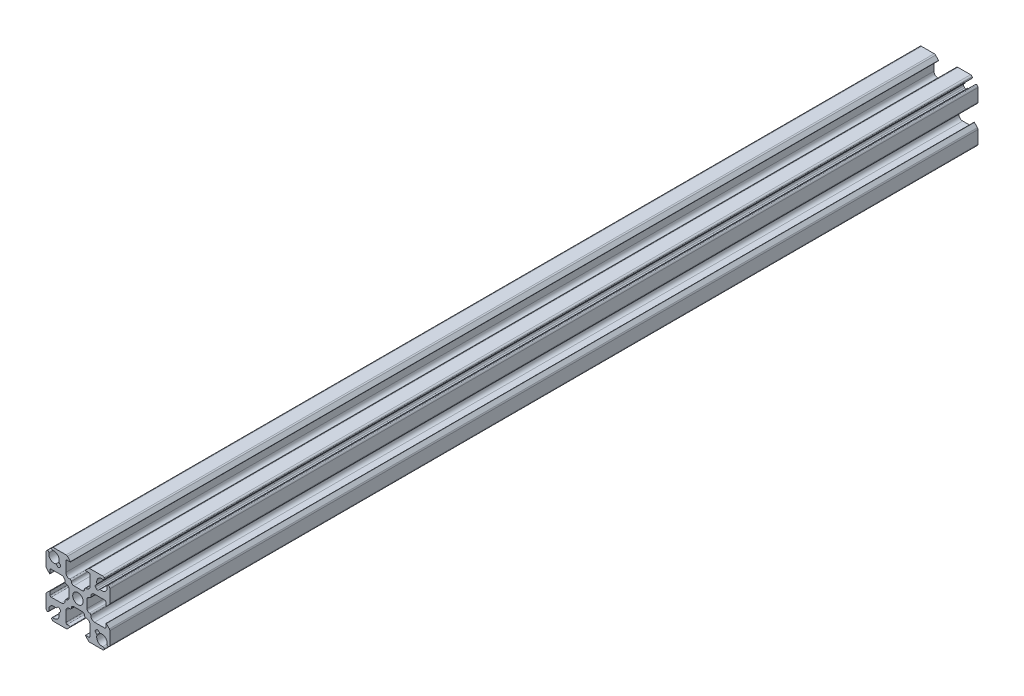
SolidWorks part; units mm, degrees
ref_plane "Front Plane" through (0, 0, 0) normal (0, 0, 1) x (1, 0, 0)
ref_plane "Top Plane" through (0, 0, 0) normal (0, 1, 0) x (1, 0, 0)
ref_plane "Right Plane" through (0, 0, 0) normal (1, 0, 0) x (0, 0, -1)
ref_plane "Plane1" through (0, 0, 0) normal (0, 0, -1) x (-1, 0, 0)
sketch "Sketch1" plane through (0, 0, 0) normal (0, 0, -1) x (-1, 0, 0)
  line L0 (-7.4885, 8.6199) -> (-6.9856, 8.117)
  line L1 (-6.9856, 7.4099) -> (-7.4099, 6.9856)
  line L2 (-8.117, 6.9856) -> (-8.6199, 7.4885)
  line L3 (-12.7, 9.7594) -> (-12.7, 4.7107)
  line L4 (-12.4803, 4.1803) -> (-11.2707, 2.9707)
  line L5 (-11.1, 3.0414) -> (-11.1, 4.325)
  line L6 (-10.6, 4.825) -> (-6.6, 4.825)
  line L7 (-5.1, 3.325) -> (-5.1, 3.15)
  line L8 (-3.6, 1.65) -> (-3.6, -1.65)
  line L9 (-5.1, -3.15) -> (-5.1, -3.325)
  line L10 (-6.6, -4.825) -> (-10.6, -4.825)
  line L11 (-11.1, -4.325) -> (-11.1, -3.0414)
  line L12 (-11.2707, -2.9707) -> (-12.4803, -4.1803)
  line L13 (-12.7, -4.7107) -> (-12.7, -9.7594)
  line L14 (-8.6199, -7.4885) -> (-8.117, -6.9856)
  line L15 (-7.4099, -6.9856) -> (-6.9856, -7.4099)
  line L16 (-6.9856, -8.117) -> (-7.4885, -8.6199)
  line L17 (-9.7594, -12.7) -> (-4.7107, -12.7)
  line L18 (-4.1803, -12.4803) -> (-2.9707, -11.2707)
  line L19 (-3.0414, -11.1) -> (-4.325, -11.1)
  line L20 (-4.825, -10.6) -> (-4.825, -6.6)
  line L21 (-3.325, -5.1) -> (-3.15, -5.1)
  line L22 (-1.65, -3.6) -> (1.65, -3.6)
  line L23 (3.15, -5.1) -> (3.325, -5.1)
  line L24 (4.825, -6.6) -> (4.825, -10.6)
  line L25 (4.325, -11.1) -> (3.0414, -11.1)
  line L26 (2.9707, -11.2707) -> (4.1803, -12.4803)
  line L27 (4.7107, -12.7) -> (9.7594, -12.7)
  line L28 (7.4885, -8.6199) -> (6.9856, -8.117)
  line L29 (6.9856, -7.4099) -> (7.4099, -6.9856)
  line L30 (8.117, -6.9856) -> (8.6199, -7.4885)
  line L31 (12.7, -9.7594) -> (12.7, -4.7107)
  line L32 (12.4803, -4.1803) -> (11.2707, -2.9707)
  line L33 (11.1, -3.0414) -> (11.1, -4.325)
  line L34 (10.6, -4.825) -> (6.6, -4.825)
  line L35 (5.1, -3.325) -> (5.1, -3.15)
  line L36 (3.6, -1.65) -> (3.6, 1.65)
  line L37 (5.1, 3.15) -> (5.1, 3.325)
  line L38 (6.6, 4.825) -> (10.6, 4.825)
  line L39 (11.1, 4.325) -> (11.1, 3.0414)
  line L40 (11.2707, 2.9707) -> (12.4803, 4.1803)
  line L41 (12.7, 4.7107) -> (12.7, 9.7594)
  line L42 (8.6199, 7.4885) -> (8.117, 6.9856)
  line L43 (7.4099, 6.9856) -> (6.9856, 7.4099)
  line L44 (6.9856, 8.117) -> (7.4885, 8.6199)
  line L45 (9.7594, 12.7) -> (4.7107, 12.7)
  line L46 (4.1803, 12.4803) -> (2.9707, 11.2707)
  line L47 (3.0414, 11.1) -> (4.325, 11.1)
  line L48 (4.825, 10.6) -> (4.825, 6.6)
  line L49 (3.325, 5.1) -> (3.15, 5.1)
  line L50 (1.65, 3.6) -> (-1.65, 3.6)
  line L51 (-3.15, 5.1) -> (-3.325, 5.1)
  line L52 (-4.825, 6.6) -> (-4.825, 10.6)
  line L53 (-4.325, 11.1) -> (-3.0414, 11.1)
  line L54 (-2.9707, 11.2707) -> (-4.1803, 12.4803)
  line L55 (-4.7107, 12.7) -> (-9.7594, 12.7)
  circle A0 centre (0, 0) radius 2.08
  arc A1 (-9.7594, 12.7) -> (-10.4266, 12.2927) centre (-9.7594, 11.95) ccw
  arc A2 (-10.4266, 12.2927) -> (-9.8933, 11.5721) centre (-9.9818, 12.0642) ccw
  arc A3 (-9.8933, 11.5721) -> (-7.5492, 8.8748) centre (-9.525, 9.525) cw
  arc A4 (-7.5492, 8.8748) -> (-7.4885, 8.6199) centre (-7.3118, 8.7967) ccw
  arc A5 (-6.9856, 8.117) -> (-6.9856, 7.4099) centre (-7.3392, 7.7635) cw
  arc A6 (-7.4099, 6.9856) -> (-8.117, 6.9856) centre (-7.7635, 7.3392) cw
  arc A7 (-8.6199, 7.4885) -> (-8.8748, 7.5492) centre (-8.7967, 7.3118) ccw
  arc A8 (-8.8748, 7.5492) -> (-11.5721, 9.8933) centre (-9.525, 9.525) cw
  arc A9 (-11.5721, 9.8933) -> (-12.2927, 10.4266) centre (-12.0642, 9.9818) ccw
  arc A10 (-12.2927, 10.4266) -> (-12.7, 9.7594) centre (-11.95, 9.7594) ccw
  arc A11 (-12.7, 4.7107) -> (-12.4803, 4.1803) centre (-11.95, 4.7107) ccw
  arc A12 (-11.2707, 2.9707) -> (-11.1, 3.0414) centre (-11.2, 3.0414) ccw
  arc A13 (-11.1, 4.325) -> (-10.6, 4.825) centre (-10.6, 4.325) cw
  arc A14 (-6.6, 4.825) -> (-5.1, 3.325) centre (-6.6, 3.325) cw
  arc A15 (-5.1, 3.15) -> (-4.6, 2.65) centre (-4.6, 3.15) ccw
  arc A16 (-4.6, 2.65) -> (-3.6, 1.65) centre (-4.6, 1.65) cw
  arc A17 (-3.6, -1.65) -> (-4.6, -2.65) centre (-4.6, -1.65) cw
  arc A18 (-4.6, -2.65) -> (-5.1, -3.15) centre (-4.6, -3.15) ccw
  arc A19 (-5.1, -3.325) -> (-6.6, -4.825) centre (-6.6, -3.325) cw
  arc A20 (-10.6, -4.825) -> (-11.1, -4.325) centre (-10.6, -4.325) cw
  arc A21 (-11.1, -3.0414) -> (-11.2707, -2.9707) centre (-11.2, -3.0414) ccw
  arc A22 (-12.4803, -4.1803) -> (-12.7, -4.7107) centre (-11.95, -4.7107) ccw
  arc A23 (-12.7, -9.7594) -> (-12.2927, -10.4266) centre (-11.95, -9.7594) ccw
  arc A24 (-12.2927, -10.4266) -> (-11.5721, -9.8933) centre (-12.0642, -9.9818) ccw
  arc A25 (-11.5721, -9.8933) -> (-8.8748, -7.5492) centre (-9.525, -9.525) cw
  arc A26 (-8.8748, -7.5492) -> (-8.6199, -7.4885) centre (-8.7967, -7.3118) ccw
  arc A27 (-8.117, -6.9856) -> (-7.4099, -6.9856) centre (-7.7635, -7.3392) cw
  arc A28 (-6.9856, -7.4099) -> (-6.9856, -8.117) centre (-7.3392, -7.7635) cw
  arc A29 (-7.4885, -8.6199) -> (-7.5492, -8.8748) centre (-7.3118, -8.7967) ccw
  arc A30 (-7.5492, -8.8748) -> (-9.8933, -11.5721) centre (-9.525, -9.525) cw
  arc A31 (-9.8933, -11.5721) -> (-10.4266, -12.2927) centre (-9.9818, -12.0642) ccw
  arc A32 (-10.4266, -12.2927) -> (-9.7594, -12.7) centre (-9.7594, -11.95) ccw
  arc A33 (-4.7107, -12.7) -> (-4.1803, -12.4803) centre (-4.7107, -11.95) ccw
  arc A34 (-2.9707, -11.2707) -> (-3.0414, -11.1) centre (-3.0414, -11.2) ccw
  arc A35 (-4.325, -11.1) -> (-4.825, -10.6) centre (-4.325, -10.6) cw
  arc A36 (-4.825, -6.6) -> (-3.325, -5.1) centre (-3.325, -6.6) cw
  arc A37 (-3.15, -5.1) -> (-2.65, -4.6) centre (-3.15, -4.6) ccw
  arc A38 (-2.65, -4.6) -> (-1.65, -3.6) centre (-1.65, -4.6) cw
  arc A39 (1.65, -3.6) -> (2.65, -4.6) centre (1.65, -4.6) cw
  arc A40 (2.65, -4.6) -> (3.15, -5.1) centre (3.15, -4.6) ccw
  arc A41 (3.325, -5.1) -> (4.825, -6.6) centre (3.325, -6.6) cw
  arc A42 (4.825, -10.6) -> (4.325, -11.1) centre (4.325, -10.6) cw
  arc A43 (3.0414, -11.1) -> (2.9707, -11.2707) centre (3.0414, -11.2) ccw
  arc A44 (4.1803, -12.4803) -> (4.7107, -12.7) centre (4.7107, -11.95) ccw
  arc A45 (9.7594, -12.7) -> (10.4266, -12.2927) centre (9.7594, -11.95) ccw
  arc A46 (10.4266, -12.2927) -> (9.8933, -11.5721) centre (9.9818, -12.0642) ccw
  arc A47 (9.8933, -11.5721) -> (7.5492, -8.8748) centre (9.525, -9.525) cw
  arc A48 (7.5492, -8.8748) -> (7.4885, -8.6199) centre (7.3118, -8.7967) ccw
  arc A49 (6.9856, -8.117) -> (6.9856, -7.4099) centre (7.3392, -7.7635) cw
  arc A50 (7.4099, -6.9856) -> (8.117, -6.9856) centre (7.7635, -7.3392) cw
  arc A51 (8.6199, -7.4885) -> (8.8748, -7.5492) centre (8.7967, -7.3118) ccw
  arc A52 (8.8748, -7.5492) -> (11.5721, -9.8933) centre (9.525, -9.525) cw
  arc A53 (11.5721, -9.8933) -> (12.2927, -10.4266) centre (12.0642, -9.9818) ccw
  arc A54 (12.2927, -10.4266) -> (12.7, -9.7594) centre (11.95, -9.7594) ccw
  arc A55 (12.7, -4.7107) -> (12.4803, -4.1803) centre (11.95, -4.7107) ccw
  arc A56 (11.2707, -2.9707) -> (11.1, -3.0414) centre (11.2, -3.0414) ccw
  arc A57 (11.1, -4.325) -> (10.6, -4.825) centre (10.6, -4.325) cw
  arc A58 (6.6, -4.825) -> (5.1, -3.325) centre (6.6, -3.325) cw
  arc A59 (5.1, -3.15) -> (4.6, -2.65) centre (4.6, -3.15) ccw
  arc A60 (4.6, -2.65) -> (3.6, -1.65) centre (4.6, -1.65) cw
  arc A61 (3.6, 1.65) -> (4.6, 2.65) centre (4.6, 1.65) cw
  arc A62 (4.6, 2.65) -> (5.1, 3.15) centre (4.6, 3.15) ccw
  arc A63 (5.1, 3.325) -> (6.6, 4.825) centre (6.6, 3.325) cw
  arc A64 (10.6, 4.825) -> (11.1, 4.325) centre (10.6, 4.325) cw
  arc A65 (11.1, 3.0414) -> (11.2707, 2.9707) centre (11.2, 3.0414) ccw
  arc A66 (12.4803, 4.1803) -> (12.7, 4.7107) centre (11.95, 4.7107) ccw
  arc A67 (12.7, 9.7594) -> (12.2927, 10.4266) centre (11.95, 9.7594) ccw
  arc A68 (12.2927, 10.4266) -> (11.5721, 9.8933) centre (12.0642, 9.9818) ccw
  arc A69 (11.5721, 9.8933) -> (8.8748, 7.5492) centre (9.525, 9.525) cw
  arc A70 (8.8748, 7.5492) -> (8.6199, 7.4885) centre (8.7967, 7.3118) ccw
  arc A71 (8.117, 6.9856) -> (7.4099, 6.9856) centre (7.7635, 7.3392) cw
  arc A72 (6.9856, 7.4099) -> (6.9856, 8.117) centre (7.3392, 7.7635) cw
  arc A73 (7.4885, 8.6199) -> (7.5492, 8.8748) centre (7.3118, 8.7967) ccw
  arc A74 (7.5492, 8.8748) -> (9.8933, 11.5721) centre (9.525, 9.525) cw
  arc A75 (9.8933, 11.5721) -> (10.4266, 12.2927) centre (9.9818, 12.0642) ccw
  arc A76 (10.4266, 12.2927) -> (9.7594, 12.7) centre (9.7594, 11.95) ccw
  arc A77 (4.7107, 12.7) -> (4.1803, 12.4803) centre (4.7107, 11.95) ccw
  arc A78 (2.9707, 11.2707) -> (3.0414, 11.1) centre (3.0414, 11.2) ccw
  arc A79 (4.325, 11.1) -> (4.825, 10.6) centre (4.325, 10.6) cw
  arc A80 (4.825, 6.6) -> (3.325, 5.1) centre (3.325, 6.6) cw
  arc A81 (3.15, 5.1) -> (2.65, 4.6) centre (3.15, 4.6) ccw
  arc A82 (2.65, 4.6) -> (1.65, 3.6) centre (1.65, 4.6) cw
  arc A83 (-1.65, 3.6) -> (-2.65, 4.6) centre (-1.65, 4.6) cw
  arc A84 (-2.65, 4.6) -> (-3.15, 5.1) centre (-3.15, 4.6) ccw
  arc A85 (-3.325, 5.1) -> (-4.825, 6.6) centre (-3.325, 6.6) cw
  arc A86 (-4.825, 10.6) -> (-4.325, 11.1) centre (-4.325, 10.6) cw
  arc A87 (-3.0414, 11.1) -> (-2.9707, 11.2707) centre (-3.0414, 11.2) ccw
  arc A88 (-4.1803, 12.4803) -> (-4.7107, 12.7) centre (-4.7107, 11.95) ccw
extrude "Boss-Extrude1" add sketch "Sketch1" against normal mid plane 345.1098
hole_wizard "Tap Drill for M6x1.0 Tap2" positions "Sketch3" profile "Sketch2" hole size "M6x1.0" standard "ANSI Metric" end condition through all
sketch "Sketch3" plane through (3.6, 0, 0) normal (1, 0, 0) x (0, 0, -1)
  point P0 (-121.3429, -5.308)
  point P3 (14.5471, -5.308)
  point P6 (-121.3429, -5.308)
sketch "Sketch2" plane through (3.6, -5.308, 121.3429) normal (0, 1, 0) x (0, 0, -1)
  line L0 (0, 0) -> (0, 16.3)
  line L1 (0, 16.3) -> (2.5, 16.3)
  line L2 (2.5, 16.3) -> (2.5, 0)
  line L5 (2.5, 0) -> (0, 0)
  line L11 (0, -6.35) -> (0, 107.95) construction
  dimension "Thru Hole Dia." = 5
  dimension "Thru Hole Depth" = 16.3
hole_wizard "Tap Drill for M6x1.0 Tap1" positions "Sketch5" profile "Sketch4" hole size "M6x1.0" standard "ANSI Metric" end condition through all
sketch "Sketch5" plane through (-3.6, 0, 0) normal (-1, 0, 0) x (0, 0, 1)
  point P0 (132.5549, 0)
  point P3 (12.5549, 0)
  point P6 (-107.4451, 0)
sketch "Sketch4" plane through (-3.6, 0, 132.5549) normal (0, 1, 0) x (0, 0, 1)
  line L0 (0, 0) -> (0, 16.3)
  line L1 (0, 16.3) -> (2.5, 16.3)
  line L2 (2.5, 16.3) -> (2.5, 0)
  line L5 (2.5, 0) -> (0, 0)
  line L11 (0, -6.35) -> (0, 107.95) construction
  dimension "Thru Hole Dia." = 5
  dimension "Thru Hole Depth" = 16.3
